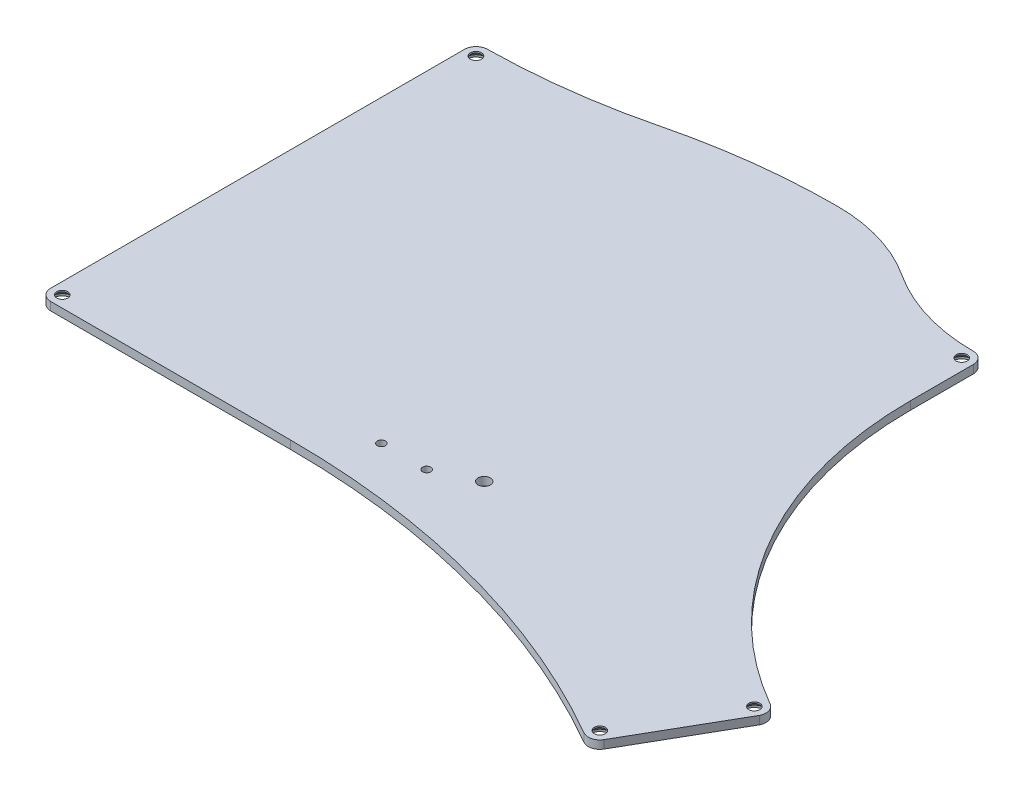
SolidWorks part; units mm, degrees
ref_plane "Front Plane" through (0, 0, 0) normal (0, 0, 1) x (1, 0, 0)
ref_plane "Top Plane" through (0, 0, 0) normal (0, 1, 0) x (1, 0, 0)
ref_plane "Right Plane" through (0, 0, 0) normal (1, 0, 0) x (0, 0, -1)
sketch "Sketch1" plane through (0, 0, 0) normal (0, 1, 0) x (1, 0, 0)
  line L45 (10.2215, -9.1905) -> (10.2215, 6.0953)
  line L46 (44.2922, -117.6593) -> (58.0808, -93.6765)
  line L47 (-115.0785, -92.7047) -> (-56.8659, -92.7047)
  line L48 (-117.8785, 10.5953) -> (-117.8785, -89.9047)
  line L49 (10.2215, -9.1905) -> (10.2215, 6.0953)
  line L50 (44.2922, -117.6593) -> (58.0808, -93.6765)
  line L51 (-115.0785, -92.7047) -> (-56.8659, -92.7047)
  line L52 (-117.8785, 10.5953) -> (-117.8785, -89.9047)
  circle A11 centre (-24.5785, -77.9047) radius 1.5
  circle A83 centre (-115.0785, 10.5953) radius 1.35
  circle A84 centre (7.4215, 6.0953) radius 1.35
  circle A85 centre (55.5716, -92.4231) radius 1.35
  circle A86 centre (41.8648, -116.2636) radius 1.35
  circle A87 centre (-115.0785, -89.9047) radius 1.35
  circle A88 centre (-115.0785, -89.9047) radius 1.35 construction
  arc A94 (-39.5785, 22.8953) -> (-77.8982, 18.203) centre (-39.5785, -135.9194) ccw
  arc A95 (-17.2824, 16.2539) -> (-39.5785, 22.8953) centre (-39.5785, -17.8511) ccw
  arc A96 (-17.2824, 16.2539) -> (7.4215, 8.8953) centre (7.4215, 54.0417) ccw
  arc A97 (10.2215, 6.0953) -> (7.4215, 8.8953) centre (7.4215, 6.0953) ccw
  arc A98 (10.2215, -9.1905) -> (56.9696, -89.9915) centre (103.425, -9.1905) ccw
  arc A99 (58.0808, -93.6765) -> (56.9696, -89.9915) centre (55.5716, -92.4231) ccw
  arc A100 (40.4692, -118.6911) -> (44.2922, -117.6593) centre (41.8648, -116.2636) ccw
  arc A101 (40.4692, -118.6911) -> (-56.8659, -92.7047) centre (-56.8659, -287.9882) ccw
  arc A102 (-117.8785, -89.9047) -> (-115.0785, -92.7047) centre (-115.0785, -89.9047) ccw
  arc A103 (-115.1157, 13.395) -> (-117.8785, 10.5953) centre (-115.0785, 10.5953) ccw
  arc A104 (-115.1157, 13.395) -> (-77.8982, 18.203) centre (-117.2794, 176.5954) ccw
  arc A105 (-39.5785, 22.8953) -> (-77.8982, 18.203) centre (-39.5785, -135.9194) ccw
  arc A106 (-17.2824, 16.2539) -> (-39.5785, 22.8953) centre (-39.5785, -17.8511) ccw
  arc A107 (-17.2824, 16.2539) -> (7.4215, 8.8953) centre (7.4215, 54.0417) ccw
  arc A108 (10.2215, 6.0953) -> (7.4215, 8.8953) centre (7.4215, 6.0953) ccw
  arc A109 (10.2215, -9.1905) -> (56.9696, -89.9915) centre (103.425, -9.1905) ccw
  arc A110 (58.0808, -93.6765) -> (56.9696, -89.9915) centre (55.5716, -92.4231) ccw
  arc A111 (40.4692, -118.6911) -> (44.2922, -117.6593) centre (41.8648, -116.2636) ccw
  arc A112 (40.4692, -118.6911) -> (-56.8659, -92.7047) centre (-56.8659, -287.9882) ccw
  arc A113 (-117.8785, -89.9047) -> (-115.0785, -92.7047) centre (-115.0785, -89.9047) ccw
  arc A114 (-115.1157, 13.395) -> (-117.8785, 10.5953) centre (-115.0785, 10.5953) ccw
  arc A115 (-115.1157, 13.395) -> (-77.8982, 18.203) centre (-117.2794, 176.5954) ccw
  dimension "D2" = 3
  dimension "D3" = 14.8
  dimension "D4" = 93.3
  dimension "D1" = 0.2
extrude "Boss-Extrude1" add sketch "Sketch1" against normal blind 2
sketch "Sketch2" plane through (0, -2, 0) normal (0, -1, 0) x (1, 0, 0)
  circle A0 centre (-115.0785, -10.5953) radius 2.5
  circle A1 centre (7.4215, -6.0953) radius 2.5
  circle A4 centre (41.8648, 116.2636) radius 2.5
  circle A5 centre (-115.0785, 89.9047) radius 2.5
  circle A6 centre (55.5716, 92.4231) radius 2.5
  dimension "D1" = 5
extrude "Cut-Extrude1" cut sketch "Sketch2" against normal blind 1.7
chamfer "Chamfer1" distance 1.2 angle 45 5 edges at (-115.0785, -0.3, 87.4047) (41.8648, -0.3, 113.7636) (55.5716, -0.3, 89.9231) (7.4215, -0.3, -8.5953) (-115.0785, -0.3, -13.0953)
sketch "Sketch3" plane through (0, -2, 0) normal (0, -1, 0) x (1, 0, 0)
  line L2 (-115.0785, 92.7047) -> (-56.8659, 92.7047) construction
  line L3 (-117.8785, -10.5953) -> (-117.8785, 89.9047) construction
  circle A0 centre (-45.0785, 82.3847) radius 1
  circle A1 centre (-34.0785, 82.3847) radius 1
  point P8 (0, 0)
  dimension "D4" = 2
  dimension "D1" = 11
  dimension "D2" = 10.32
  dimension "D3" = 72.8
extrude "Cut-Extrude2" cut sketch "Sketch3" against normal through all
